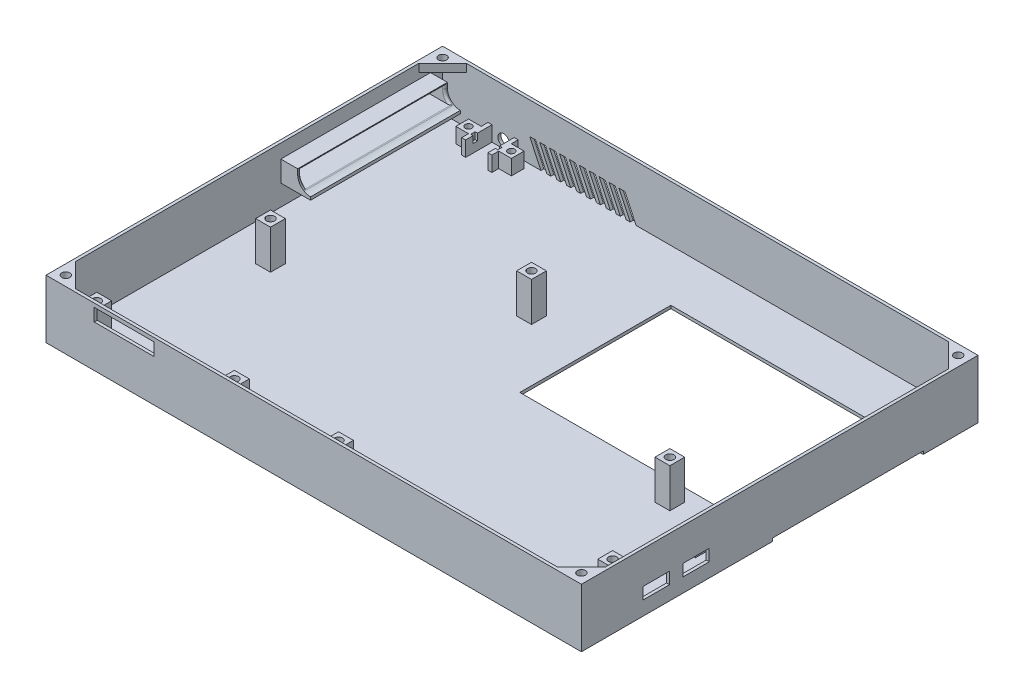
SolidWorks part; units mm, degrees
material "PLA"
ref_plane "Спереди" through (0, 0, 0) normal (0, 0, 1) x (1, 0, 0)
ref_plane "Сверху" through (0, 0, 0) normal (0, 1, 0) x (1, 0, 0)
ref_plane "Справа" through (0, 0, 0) normal (1, 0, 0) x (0, 0, -1)
sketch "Эскиз1" plane through (0, 0, 0) normal (0, 1, 0) x (1, 0, 0)
  line L1 (135, 100) -> (-135, 100)
  line L2 (135, 100) -> (135, -100)
  line L3 (135, -100) -> (-135, -100)
  line L4 (-135, 100) -> (-135, -100)
  line L5 (135, 100) -> (-135, -100) construction
  line L6 (135, -100) -> (-135, 100) construction
  point P0 (0, 0)
  dimension "D1" = 200
  dimension "D2" = 270
extrude "Бобышка-Вытянуть1" add sketch "Эскиз1" along normal blind 1.5
sketch "Эскиз2" plane through (0, 1.5, 0) normal (0, 1, 0) x (1, 0, 0)
  line L0 (133.5, 98.5) -> (-133.5, 98.5)
  line L1 (-133.5, 98.5) -> (-133.5, -98.5)
  line L2 (-133.5, -98.5) -> (-110.7, -98.5)
  line L3 (133.5, -98.5) -> (133.5, 98.5)
  line L4 (-135, 100) -> (-135, -100)
  line L5 (-135, -100) -> (135, -100)
  line L6 (135, -100) -> (135, 100)
  line L7 (135, 100) -> (-135, 100)
  line L8 (-135, 100) -> (-135, -100)
  line L9 (-135, -100) -> (-110.7, -100)
  line L10 (135, -100) -> (135, 100)
  line L11 (135, 100) -> (-135, 100)
  line L12 (-110.7, -98.5) -> (-110.7, -100)
  line L14 (-80.5, -98.5) -> (-80.5, -100)
  line L16 (-80.5, -98.5) -> (133.5, -98.5)
  line L17 (-80.5, -100) -> (135, -100)
  line L18 (-133.5, -98.5) -> (133.5, -98.5) construction
  line L20 (-135, -100) -> (135, -100) construction
  dimension "D3" = 24.3
  dimension "D4" = 54.5
  dimension "D1" = 0
  dimension "D2" = 1.5
extrude "Бобышка-Вытянуть2" add sketch "Эскиз2" along normal offset from surface (28 mm away) 7 offset beyond the face yes
sketch "Эскиз3" plane through (0, 1.5, 0) normal (0, 1, 0) x (1, 0, 0)
  line L1 (-110.7, -98.5) -> (-80.5, -98.5)
  line L2 (-110.7, -98.5) -> (-110.7, -100)
  line L3 (-110.7, -100) -> (-80.5, -100)
  line L4 (-80.5, -98.5) -> (-80.5, -100)
extrude "Бобышка-Вытянуть3" add sketch "Эскиз3" along normal blind 19.7
sketch "Эскиз4" plane through (-110.7, 0, 0) normal (1, 0, 0) x (0, 0, -1)
  line L0 (-100, 29.5) -> (-100, 21.2) construction
  line L1 (-98.5, 29.5) -> (-100, 29.5)
  line L2 (-98.5, 29.5) -> (-98.5, 27.6)
  line L3 (-98.5, 27.6) -> (-100, 27.6)
  line L4 (-100, 29.5) -> (-100, 27.6)
  dimension "D1" = 1.9
extrude "Бобышка-Вытянуть4" add sketch "Эскиз4" along normal up to surface (30.2 mm away) up to face at (-80.5, 25.35, 99.25)
sketch "Эскиз5" plane through (135, 0, 0) normal (1, 0, 0) x (0, 0, -1)
  line L0 (-100, 29.5) -> (-100, 0) construction
  line L1 (-55.55, 13) -> (-68.85, 13)
  line L2 (-55.55, 13) -> (-55.55, 7.1)
  line L3 (-55.55, 7.1) -> (-68.85, 7.1)
  line L4 (-68.85, 13) -> (-68.85, 7.1)
  line L5 (-55.55, 13) -> (-68.85, 7.1) construction
  line L6 (-55.55, 7.1) -> (-68.85, 13) construction
  line L7 (-35.55, 13) -> (-48.85, 13)
  line L8 (-35.55, 13) -> (-35.55, 7.1)
  line L9 (-35.55, 7.1) -> (-48.85, 7.1)
  line L10 (-48.85, 13) -> (-48.85, 7.1)
  line L11 (-35.55, 13) -> (-48.85, 7.1) construction
  line L12 (-35.55, 7.1) -> (-48.85, 13) construction
  line L13 (-100, 0) -> (100, 0) construction
  point P0 (-62.2, 10.05)
  point P5 (-42.2, 10.05)
  dimension "D1" = 13.3
  dimension "D2" = 5.9
  dimension "D3" = 6.7
  dimension "D4" = 31.15
  dimension "D5" = 13
extrude "Вырез-Вытянуть1" cut sketch "Эскиз5" against normal up to surface (1.5 mm away) up to face at (133.5, 15.5, 0)
sketch "Эскиз10" plane through (0, 1.5, 0) normal (0, 1, 0) x (1, 0, 0)
  line L0 (133.5, -14.85) -> (133.5, -98.5) construction
  line L1 (124.175, -24.225) -> (116.675, -24.225)
  line L2 (124.175, -24.225) -> (124.175, -31.725)
  line L3 (124.175, -31.725) -> (116.675, -31.725)
  line L4 (116.675, -24.225) -> (116.675, -31.725)
  line L5 (124.175, -24.225) -> (116.675, -31.725) construction
  line L6 (124.175, -31.725) -> (116.675, -24.225) construction
  line L7 (114.55, -56.3) -> (107.05, -56.3)
  line L8 (114.55, -56.3) -> (114.55, -63.8)
  line L9 (114.55, -63.8) -> (107.05, -63.8)
  line L10 (107.05, -56.3) -> (107.05, -63.8)
  line L11 (114.55, -56.3) -> (107.05, -63.8) construction
  line L12 (114.55, -63.8) -> (107.05, -56.3) construction
  line L13 (115.175, -89.275) -> (107.675, -89.275)
  line L14 (115.175, -89.275) -> (115.175, -96.775)
  line L15 (115.175, -96.775) -> (107.675, -96.775)
  line L16 (107.675, -89.275) -> (107.675, -96.775)
  line L17 (115.175, -89.275) -> (107.675, -96.775) construction
  line L18 (115.175, -96.775) -> (107.675, -89.275) construction
  line L19 (133.5, -98.5) -> (-133.5, -98.5) construction
  point P0 (120.425, -27.975)
  point P5 (110.8, -60.05)
  point P10 (111.425, -93.025)
  dimension "D1" = 13.075
  dimension "D2" = 70.525
  dimension "D3" = 22.7
  dimension "D4" = 38.45
  dimension "D5" = 22.075
  dimension "D6" = 5.475
  dimension "D7" = 7.5
extrude "Бобышка-Вытянуть6" add sketch "Эскиз10" along normal blind 6.9
sketch "Эскиз11" plane through (0, 1.5, 0) normal (0, 1, 0) x (1, 0, 0)
  line L1 (-46.7446, -85.75) -> (-54.2446, -85.75)
  line L2 (-46.7446, -85.75) -> (-46.7446, -93.25)
  line L3 (-46.7446, -93.25) -> (-54.2446, -93.25)
  line L4 (-54.2446, -85.75) -> (-54.2446, -93.25)
  line L5 (-46.7446, -85.75) -> (-54.2446, -93.25) construction
  line L6 (-46.7446, -93.25) -> (-54.2446, -85.75) construction
  line L7 (-19.0224, 28.8491) -> (-26.5224, 28.8491)
  line L8 (-19.0224, 28.8491) -> (-19.0224, 36.3491)
  line L9 (-19.0224, 36.3491) -> (-26.5224, 36.3491)
  line L10 (-26.5224, 28.8491) -> (-26.5224, 36.3491)
  line L11 (-19.0224, 28.8491) -> (-26.5224, 36.3491) construction
  line L12 (-19.0224, 36.3491) -> (-26.5224, 28.8491) construction
  line L13 (-115.5446, -93.8424) -> (-123.0446, -93.8424)
  line L14 (-115.5446, -93.8424) -> (-115.5446, -86.3424)
  line L15 (-115.5446, -86.3424) -> (-123.0446, -86.3424)
  line L16 (-123.0446, -93.8424) -> (-123.0446, -86.3424)
  line L17 (-115.5446, -93.8424) -> (-123.0446, -86.3424) construction
  line L18 (-115.5446, -86.3424) -> (-123.0446, -93.8424) construction
  line L19 (-107.65, -14.1324) -> (-115.15, -14.1324)
  line L20 (-107.65, -14.1324) -> (-107.65, -6.6324)
  line L21 (-107.65, -6.6324) -> (-115.15, -6.6324)
  line L22 (-115.15, -14.1324) -> (-115.15, -6.6324)
  line L23 (-107.65, -14.1324) -> (-115.15, -6.6324) construction
  line L24 (-107.65, -6.6324) -> (-115.15, -14.1324) construction
  line L25 (97.2279, -17.6196) -> (89.7279, -17.6196)
  line L26 (97.2279, -17.6196) -> (97.2279, -10.1196)
  line L27 (97.2279, -10.1196) -> (89.7279, -10.1196)
  line L28 (89.7279, -17.6196) -> (89.7279, -10.1196)
  line L29 (97.2279, -17.6196) -> (89.7279, -10.1196) construction
  line L30 (97.2279, -10.1196) -> (89.7279, -17.6196) construction
  line L31 (94.0554, -99.0196) -> (86.5554, -99.0196)
  line L32 (94.0554, -99.0196) -> (94.0554, -91.5196)
  line L33 (94.0554, -91.5196) -> (86.5554, -91.5196)
  line L34 (86.5554, -99.0196) -> (86.5554, -91.5196)
  line L35 (94.0554, -99.0196) -> (86.5554, -91.5196) construction
  line L36 (94.0554, -91.5196) -> (86.5554, -99.0196) construction
  line L37 (6.3554, -93.8285) -> (-1.1446, -93.8285)
  line L38 (6.3554, -93.8285) -> (6.3554, -86.3285)
  line L39 (6.3554, -86.3285) -> (-1.1446, -86.3285)
  line L40 (-1.1446, -93.8285) -> (-1.1446, -86.3285)
  line L41 (6.3554, -93.8285) -> (-1.1446, -86.3285) construction
  line L42 (6.3554, -86.3285) -> (-1.1446, -93.8285) construction
  line L44 (-133.5, 98.5) -> (133.5, 98.5) construction
  line L45 (-133.5, -98.5) -> (-133.5, 98.5) construction
  line L47 (133.5, -98.5) -> (-133.5, -98.5) construction
  line L48 (133.5, 98.5) -> (133.5, -98.5) construction
  point P0 (-50.4946, -89.5)
  point P5 (-22.7724, 32.5991)
  point P10 (-119.2946, -90.0924)
  point P15 (-111.4, -10.3824)
  point P20 (93.4779, -13.8696)
  point P25 (90.3054, -95.2696)
  point P30 (2.6054, -90.0785)
  dimension "D1" = 7.5
  dimension "D2" = 65.9009
  dimension "D3" = 110.7276
  dimension "D4" = 108.8824
  dimension "D5" = 22.1
  dimension "D6" = 8.4076
  dimension "D7" = 14.2054
  dimension "D8" = 8.4215
  dimension "D9" = 130.8946
  dimension "D10" = 9
  dimension "D11" = 83.0054
  dimension "D12" = 3.2304
  dimension "D13" = 43.1946
  dimension "D14" = 84.6304
  dimension "D15" = 40.0221
extrude "Бобышка-Вытянуть7" add sketch "Эскиз11" along normal blind 19.7
sketch "Эскиз12" plane through (0, 1.5, 0) normal (0, 1, 0) x (1, 0, 0)
  line L1 (135, 72.4) -> (7.7, 72.4)
  line L2 (135, 72.4) -> (135, -3.75)
  line L3 (135, -3.75) -> (7.7, -3.75)
  line L4 (7.7, 72.4) -> (7.7, -3.75)
  line L5 (-133.5, 98.5) -> (133.5, 98.5) construction
  line L6 (135, -100) -> (135, 100) construction
  dimension "D1" = 76.15
  dimension "D2" = 127.3
  dimension "D3" = 26.1
extrude "Вырез-Вытянуть2" cut sketch "Эскиз12" against normal through all
sketch "Эскиз14" plane through (0, 21.2, 0) normal (0, 1, 0) x (1, 0, 0)
  line L0 (-115.15, -6.6324) -> (-107.65, -14.1324) construction
  line L1 (-107.65, -6.6324) -> (-115.15, -14.1324) construction
  line L2 (-19.0224, 36.3491) -> (-26.5224, 28.8491) construction
  line L3 (-26.5224, 36.3491) -> (-19.0224, 28.8491) construction
  line L4 (-123.0446, -86.3424) -> (-115.5446, -93.8424) construction
  line L5 (-115.5446, -86.3424) -> (-123.0446, -93.8424) construction
  line L6 (-54.2446, -85.75) -> (-46.7446, -93.25) construction
  line L7 (-46.7446, -85.75) -> (-54.2446, -93.25) construction
  line L8 (-1.1446, -86.3285) -> (6.3554, -93.8285) construction
  line L9 (6.3554, -86.3285) -> (-1.1446, -93.8285) construction
  line L10 (94.0554, -91.5196) -> (86.5554, -99.0196) construction
  line L11 (94.0554, -91.5196) -> (86.5554, -91.5196) construction
  line L12 (94.0554, -91.5196) -> (94.0554, -99.0196) construction
  line L13 (94.0554, -99.0196) -> (86.5554, -99.0196) construction
  line L14 (86.5554, -91.5196) -> (86.5554, -99.0196) construction
  line L15 (94.0554, -99.0196) -> (86.5554, -91.5196) construction
  line L22 (97.2279, -10.1196) -> (89.7279, -17.6196) construction
  line L23 (97.2279, -17.6196) -> (89.7279, -10.1196) construction
  circle A0 centre (-22.7724, 32.5991) radius 2.05
  circle A1 centre (-111.4, -10.3824) radius 2.05
  circle A2 centre (-119.2946, -90.0924) radius 2.05
  circle A3 centre (-50.4946, -89.5) radius 2.05
  circle A4 centre (2.6054, -90.0785) radius 2.05
  circle A5 centre (90.3054, -95.2696) radius 2.05
  circle A6 centre (93.4779, -13.8696) radius 2.05
  dimension "D1" = 4.1
extrude "Вырез-Вытянуть4" cut sketch "Эскиз14" against normal blind 5
sketch "Эскиз15" plane through (0, 8.4, 0) normal (0, 1, 0) x (1, 0, 0)
  line L0 (124.175, -24.225) -> (116.675, -31.725) construction
  line L1 (116.675, -24.225) -> (124.175, -31.725) construction
  line L2 (107.05, -56.3) -> (114.55, -63.8) construction
  line L3 (114.55, -56.3) -> (107.05, -63.8) construction
  line L4 (107.675, -89.275) -> (115.175, -96.775) construction
  line L5 (115.175, -89.275) -> (107.675, -96.775) construction
  circle A0 centre (111.425, -93.025) radius 2.05
  circle A1 centre (110.8, -60.05) radius 2.05
  circle A2 centre (120.425, -27.975) radius 2.05
  dimension "D1" = 4.1
extrude "Вырез-Вытянуть5" cut sketch "Эскиз15" against normal blind 5
sketch "Эскиз16" plane through (0, 0, -100) normal (0, 0, -1) x (-1, 0, 0)
  line L0 (133.5, 22.5) -> (125, 22.5)
  line L1 (133.5, 29.5) -> (133.5, 1.5) construction
  line L2 (125, 22.5) -> (125, 20)
  line L3 (118.5, 13.5) -> (133.5, 13.5)
  line L4 (133.5, 13.5) -> (133.5, 22.5)
  line L5 (133.5, 1.5) -> (-133.5, 1.5) construction
  arc A0 (125, 20) -> (118.5, 13.5) centre (118.5, 20) cw
  dimension "D3" = 6.5
  dimension "D1" = 8.5
  dimension "D2" = 2.5
  dimension "D4" = 21
  dimension "D5" = 15
extrude "Бобышка-Вытянуть8" add sketch "Эскиз16" against normal blind 75.5 from offset 7.5824 offset against normal yes
sketch "Эскиз18" plane through (0, 0, -16.9176) normal (0, 0, 1) x (1, 0, 0)
  line L0 (-135, 21.5) -> (-125, 21.5)
  line L1 (-135, 29.5) -> (-135, 0) construction
  line L2 (-125, 22.5) -> (-125, 20) construction
  line L3 (-125, 21.5) -> (-125, 20)
  line L4 (-135, 21.5) -> (-135, 14.5)
  line L5 (-135, 14.5) -> (-121.9641, 14.5)
  line L6 (-133.5, 22.5) -> (-125, 22.5) construction
  line L7 (-118.5, 13.5) -> (-133.5, 13.5) construction
  arc A0 (-125, 20) -> (-118.5, 13.5) centre (-118.5, 20) ccw construction
  arc A1 (-125, 20) -> (-121.9641, 14.5) centre (-118.5, 20) ccw
  dimension "D1" = 1
  dimension "D2" = 1
extrude "Вырез-Вытянуть6" cut sketch "Эскиз18" against normal offset from surface (72.5 mm away) 1.5 from offset 1.5 up to face at (-127.3692, 18.1308, -92.4176) offset against normal yes
fillet "Скругление1" radius 1 6 edges at (-125, 20.75, -90.9176) (-125, 20.75, -18.4176) (-124.1906, 16.8589, -90.9176) (-121.9641, 14.5, -54.6676) (-124.1906, 16.8589, -18.4176) (-125, 21.5, -54.6676)
sketch "Эскиз19" plane through (0, 0, -16.9176) normal (0, 0, 1) x (1, 0, 0)
  line L0 (-133.5, 13.5) -> (-133.5, 12)
  line L1 (-133.5, 29.5) -> (-133.5, 1.5) construction
  line L2 (-133.5, 13.5) -> (-118.5, 13.5)
  line L3 (-118.5, 13.5) -> (-133.5, 13.5) construction
  line L4 (-118.5, 13.5) -> (-118.5, 12)
  line L5 (-118.5, 12) -> (-133.5, 12)
  dimension "D1" = 1.5
extrude "Бобышка-Вытянуть9" add sketch "Эскиз19" against normal up to surface (75.5 mm away) up to face at (-127.3692, 18.1308, -92.4176)
sketch "Эскиз20" plane through (0, 0, -100) normal (0, 0, -1) x (-1, 0, 0)
  line L0 (135, 29.5) -> (135, 0) construction
  line L1 (89.5705, 13.5) -> (86.5705, 13.5)
  line L3 (83.9, 1.5) -> (80.9, 1.5)
  line L5 (90.9, 13.5) -> (35.9, 1.5) construction
  line L6 (90.9, 1.5) -> (35.9, 13.5) construction
  line L7 (-135, 0) -> (135, 0) construction
  line L8 (35.9, 1.5) -> (41.5705, 13.5)
  line L9 (44.5705, 13.5) -> (38.9, 1.5)
  line L10 (40.9, 1.5) -> (46.5705, 13.5)
  line L11 (49.5705, 13.5) -> (43.9, 1.5)
  line L12 (45.9, 1.5) -> (51.5705, 13.5)
  line L13 (54.5705, 13.5) -> (48.9, 1.5)
  line L14 (50.9, 1.5) -> (56.5705, 13.5)
  line L15 (59.5705, 13.5) -> (53.9, 1.5)
  line L16 (55.9, 1.5) -> (61.5705, 13.5)
  line L17 (64.5705, 13.5) -> (58.9, 1.5)
  line L18 (60.9, 1.5) -> (66.5705, 13.5)
  line L19 (69.5705, 13.5) -> (63.9, 1.5)
  line L20 (65.9, 1.5) -> (71.5705, 13.5)
  line L21 (74.5705, 13.5) -> (68.9, 1.5)
  line L22 (70.9, 1.5) -> (76.5705, 13.5)
  line L23 (79.5705, 13.5) -> (73.9, 1.5)
  line L24 (75.9, 1.5) -> (81.5705, 13.5)
  line L25 (84.5705, 13.5) -> (78.9, 1.5)
  line L26 (80.9, 1.5) -> (86.5705, 13.5)
  line L27 (89.5705, 13.5) -> (83.9, 1.5)
  line L28 (44.5705, 13.5) -> (41.5705, 13.5)
  line L29 (38.9, 1.5) -> (35.9, 1.5)
  line L30 (43.9, 1.5) -> (40.9, 1.5)
  line L31 (49.5705, 13.5) -> (46.5705, 13.5)
  line L32 (54.5705, 13.5) -> (51.5705, 13.5)
  line L33 (48.9, 1.5) -> (45.9, 1.5)
  line L34 (53.9, 1.5) -> (50.9, 1.5)
  line L35 (59.5705, 13.5) -> (56.5705, 13.5)
  line L36 (58.9, 1.5) -> (55.9, 1.5)
  line L37 (64.5705, 13.5) -> (61.5705, 13.5)
  line L38 (63.9, 1.5) -> (60.9, 1.5)
  line L39 (69.5705, 13.5) -> (66.5705, 13.5)
  line L40 (68.9, 1.5) -> (65.9, 1.5)
  line L41 (74.5705, 13.5) -> (71.5705, 13.5)
  line L42 (73.9, 1.5) -> (70.9, 1.5)
  line L43 (79.5705, 13.5) -> (76.5705, 13.5)
  line L44 (78.9, 1.5) -> (75.9, 1.5)
  line L45 (84.5705, 13.5) -> (81.5705, 13.5)
  line L46 (35.9, 13.5) -> (35.9, 1.5) construction
  line L47 (90.9, 13.5) -> (90.9, 1.5) construction
  point P0 (63.4, 7.5)
  dimension "D1" = 71.6
  dimension "D2" = 1.5
  dimension "D3" = 12
  dimension "D4" = 55
  dimension "D5" = 3
  dimension "D8" = 2
  dimension "D9" = 64.707
  dimension "D6" = 10
extrude "Вырез-Вытянуть7" cut sketch "Эскиз20" against normal up to surface (1.5 mm away) up to face at (0, 15.5, -98.5)
sketch "Эскиз21" plane through (0, 0, -100) normal (0, 0, -1) x (-1, 0, 0)
  line L0 (135, 29.5) -> (135, 0) construction
  line L1 (-135, 0) -> (135, 0) construction
  circle A0 centre (102.7, 5.325) radius 2.9
  dimension "D1" = 5.8
  dimension "D2" = 32.3
  dimension "D3" = 5.325
extrude "Вырез-Вытянуть8" cut sketch "Эскиз21" against normal up to surface (1.5 mm away) up to face at (-57.032, 8.2273, -98.5)
sketch "Эскиз22" plane through (0, 1.5, 0) normal (0, 1, 0) x (1, 0, 0)
  line L0 (-133.5, 98.5) -> (-83.9, 98.5) construction
  line L1 (-108.6, 98.5) -> (-110.6, 98.5)
  line L2 (-108.6, 98.5) -> (-108.6, 85.25)
  line L3 (-108.6, 85.25) -> (-110.6, 85.25)
  line L4 (-110.6, 98.5) -> (-110.6, 85.25)
  line L5 (-133.5, -98.5) -> (-133.5, 98.5) construction
  line L7 (-95.4, 98.5) -> (-97.4, 98.5)
  line L8 (-95.4, 98.5) -> (-95.4, 85.25)
  line L9 (-95.4, 85.25) -> (-97.4, 85.25)
  line L10 (-97.4, 98.5) -> (-97.4, 85.25)
  dimension "D1" = 24.9
  dimension "D2" = 13.25
  dimension "D3" = 2
  dimension "D4" = 36.1
extrude "Бобышка-Вытянуть10" add sketch "Эскиз22" along normal blind 7.65
sketch "Эскиз23" plane through (0, 9.15, 0) normal (0, 1, 0) x (1, 0, 0)
  line L0 (-108.6, 85.25) -> (-108.6, 98.5) construction
  line L1 (-108.6, 91.2) -> (-109.8, 91.2)
  line L2 (-108.6, 91.2) -> (-108.6, 89)
  line L3 (-108.6, 89) -> (-109.8, 89)
  line L4 (-109.8, 91.2) -> (-109.8, 89)
  line L5 (-97.4, 98.5) -> (-97.4, 85.25) construction
  line L6 (-97.4, 91.2) -> (-96.2, 91.2)
  line L7 (-97.4, 91.2) -> (-97.4, 89)
  line L8 (-97.4, 89) -> (-96.2, 89)
  line L9 (-96.2, 91.2) -> (-96.2, 89)
  line L10 (-110.6, 85.25) -> (-108.6, 85.25) construction
  dimension "D1" = 2.2
  dimension "D2" = 1.2
  dimension "D3" = 5.95
extrude "Вырез-Вытянуть9" cut sketch "Эскиз23" against normal blind 3.45
sketch "Эскиз24" plane through (0, 1.5, 0) normal (0, 1, 0) x (1, 0, 0)
  line L0 (-108.6, 91.875) -> (-97.4, 91.875) construction
  line L3 (-103, 91.875) -> (-103, 50091.875) construction
  line L4 (-108.6, 85.25) -> (-108.6, 98.5) construction
  line L5 (-108.6, 98.5) -> (-97.4, 98.5) construction
  line L6 (-110.6, 98.5) -> (-110.6, 85.25) construction
  line L7 (-117, 95.075) -> (-110.6, 95.075)
  line L8 (-117, 95.075) -> (-117, 88.675)
  line L9 (-117, 88.675) -> (-110.6, 88.675)
  line L10 (-110.6, 95.075) -> (-110.6, 88.675)
  line L11 (-117, 95.075) -> (-110.6, 88.675) construction
  line L12 (-117, 88.675) -> (-110.6, 95.075) construction
  line L13 (-89, 88.675) -> (-95.4, 88.675)
  line L14 (-95.4, 95.075) -> (-95.4, 88.675)
  line L15 (-89, 95.075) -> (-95.4, 95.075)
  line L16 (-89, 95.075) -> (-89, 88.675)
  circle A0 centre (-113.8, 91.875) radius 1.7 construction
  point P3 (-108.6, 91.875)
  point P8 (-103, 98.5)
  point P10 (-113.8, 91.875)
  dimension "D1" = 3.4
  dimension "D2" = 1.5
extrude "Бобышка-Вытянуть11" add sketch "Эскиз24" along normal up to surface (7.65 mm away) up to face at (-109.4, 9.15, -90.9875)
sketch "Эскиз25" plane through (0, 9.15, 0) normal (0, 1, 0) x (1, 0, 0)
  line L0 (-117, 95.075) -> (-110.6, 88.675) construction
  line L1 (-110.6, 95.075) -> (-117, 88.675) construction
  line L2 (-95.4, 95.075) -> (-89, 88.675) construction
  line L3 (-89, 95.075) -> (-95.4, 88.675) construction
  circle A0 centre (-113.8, 91.875) radius 1.7
  circle A1 centre (-92.2, 91.875) radius 1.7
  dimension "D1" = 3.4
extrude "Вырез-Вытянуть10" cut sketch "Эскиз25" against normal blind 3
sketch "Эскиз26" plane through (0, 29.5, 0) normal (0, 1, 0) x (1, 0, 0)
  line L0 (0, 0) -> (0, 50000) construction
  line L1 (0, 0) -> (-50000, 0) construction
  line L2 (121.5, 98.5) -> (133.5, 98.5)
  line L3 (-35.9, 98.5) -> (133.5, 98.5) construction
  line L4 (133.5, 98.5) -> (133.5, 86.5)
  line L5 (133.5, 98.5) -> (133.5, -98.5) construction
  line L6 (133.5, 86.5) -> (121.5, 98.5)
  line L7 (133.5, 98.5) -> (127.5, 92.5) construction
  line L8 (133.5, -98.5) -> (133.5, -86.5)
  line L9 (121.5, -98.5) -> (133.5, -98.5)
  line L10 (133.5, -86.5) -> (121.5, -98.5)
  line L11 (-121.5, -98.5) -> (-133.5, -98.5)
  line L12 (-133.5, -86.5) -> (-121.5, -98.5)
  line L13 (-133.5, -98.5) -> (-133.5, -86.5)
  line L14 (-133.5, 98.5) -> (-133.5, 86.5)
  line L15 (-121.5, 98.5) -> (-133.5, 98.5)
  line L16 (-133.5, 86.5) -> (-121.5, 98.5)
  circle A0 centre (130.0102, 95.0102) radius 2.05 construction
  point P16 (0, 0)
  point P17 (130.2502, 95.2502)
  point P18 (130.2773, 95.2773)
  point P28 (130.0154, 95.0154)
  dimension "D1" = 4.1
  dimension "D3" = 1.5
  dimension "D4" = 1.4398
  dimension "D2" = 12
extrude "Бобышка-Вытянуть12" add sketch "Эскиз26" against normal blind 4
sketch "Эскиз27" plane through (0, 29.5, 0) normal (0, 1, 0) x (1, 0, 0)
  line L0 (0, 0) -> (0, 50000) construction
  line L1 (0, 0) -> (-50000, 0) construction
  line L2 (135, 100) -> (127.5, 92.5) construction
  line L3 (121.5, 98.5) -> (133.5, 86.5) construction
  circle A0 centre (130.0102, 95.0102) radius 2.05
  circle A1 centre (130.0102, -95.0102) radius 2.05
  circle A2 centre (-130.0102, -95.0102) radius 2.05
  circle A3 centre (-130.0102, 95.0102) radius 2.05
  dimension "D1" = 4.1
  dimension "D2" = 1.5
extrude "Вырез-Вытянуть11" cut sketch "Эскиз27" against normal up to surface (4 mm away) up to face at (129.5, 25.5, -94.5)
